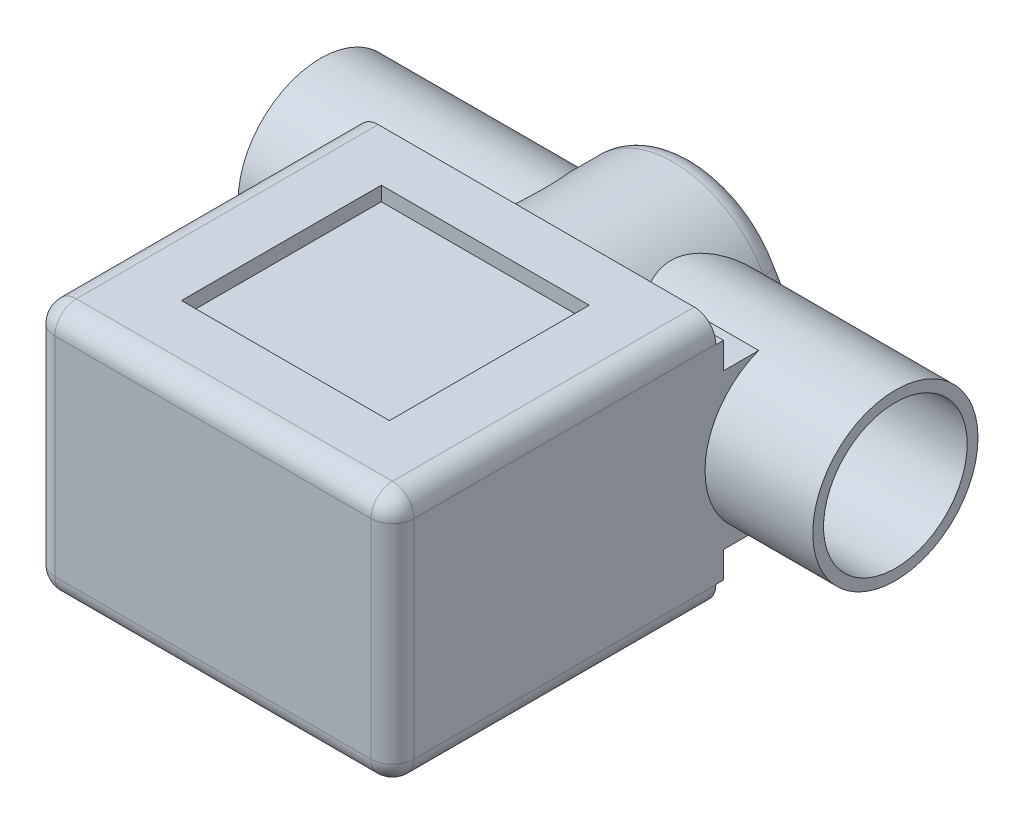
SolidWorks part; units mm, degrees
ref_plane "Alzado" through (0, 0, 0) normal (0, 0, 1) x (1, 0, 0)
ref_plane "Planta" through (0, 0, 0) normal (0, 1, 0) x (1, 0, 0)
ref_plane "Vista lateral" through (0, 0, 0) normal (1, 0, 0) x (0, 0, -1)
sketch "Croquis1" plane through (0, 0, 0) normal (0, 0, 1) x (1, 0, 0)
  line L1 (25, -17.5) -> (-25, -17.5)
  line L2 (25, -17.5) -> (25, 17.5)
  line L3 (25, 17.5) -> (-25, 17.5)
  line L4 (-25, -17.5) -> (-25, 17.5)
  line L5 (25, -17.5) -> (-25, 17.5) construction
  line L6 (25, 17.5) -> (-25, -17.5) construction
  point P0 (0, 0)
  dimension "D1" = 35
  dimension "D2" = 50
extrude "Saliente-Extruir1" add sketch "Croquis1" along normal blind 45
fillet "Redondeo1" radius 3 8 edges at (0, 17.5, 45) (25, 0, 45) (0, -17.5, 45) (-25, 0, 45) (25, -17.5, 22.5) (-25, -17.5, 22.5) (-25, 17.5, 22.5) (25, 17.5, 22.5)
sketch "Croquis3" plane through (0, 17.5, 0) normal (0, 1, 0) x (1, 0, 0)
  line L1 (-14.4727, -34.9074) -> (14.4727, -34.9074)
  line L2 (-14.4727, -34.9074) -> (-14.4727, -7.0926)
  line L3 (-14.4727, -7.0926) -> (14.4727, -7.0926)
  line L4 (14.4727, -34.9074) -> (14.4727, -7.0926)
  line L5 (-14.4727, -34.9074) -> (14.4727, -7.0926) construction
  line L6 (-14.4727, -7.0926) -> (14.4727, -34.9074) construction
  point P0 (0, -21)
extrude "Cortar-Extruir1" cut sketch "Croquis3" against normal blind 2
mirror "Simetría1" about plane through (0, 0, 0) normal (0, 1, 0) of "Cortar-Extruir1"
sketch "Croquis4" plane through (0, 0, 0) normal (1, 0, 0) x (0, 0, -1)
  line L0 (0, 0) -> (10, 0) construction
  circle A0 centre (10, 0) radius 10
  circle A1 centre (10, 0) radius 11.5
  dimension "D2" = 23
  dimension "D1" = 10
extrude "Saliente-Extruir2" add sketch "Croquis4" along normal mid plane 80
sketch "Croquis5" plane through (0, 0, 0) normal (1, 0, 0) x (0, 0, -1)
  line L0 (10, 10.7732) -> (1.0732, 10.7732)
  line L5 (1.0732, 10.7732) -> (1.0732, 14.451)
  line L6 (-2.6196, -14.451) -> (1.0732, -14.451)
  line L7 (10, -10.7732) -> (1.0732, -10.7732)
  line L8 (-2.6196, -14.451) -> (-2.6196, 14.451)
  line L9 (-2.6196, 14.451) -> (1.0732, 14.451)
  line L10 (1.0732, -14.451) -> (1.0732, -10.7732)
  line L11 (-2.6196, -14.451) -> (1.0732, 14.451) construction
  line L12 (-2.6196, 14.451) -> (-0.4271, -2.7087) construction
  arc A1 (10, 10.7732) -> (10, -10.7732) centre (10, 0) ccw
  point P0 (-0.7732, 0)
  point P3 (-0.7732, 0)
extrude "Saliente-Extruir3" add sketch "Croquis5" along normal mid plane 50
sketch "Croquis6" plane through (0, 0, -1.0732) normal (0, 0, -1) x (-1, 0, 0)
  circle A0 centre (0, 0) radius 14.451
extrude "Saliente-Extruir4" add sketch "Croquis6" along normal blind 21
fillet "Redondeo2" radius 3 1 edges at (-14.451, 0, -22.0732)
